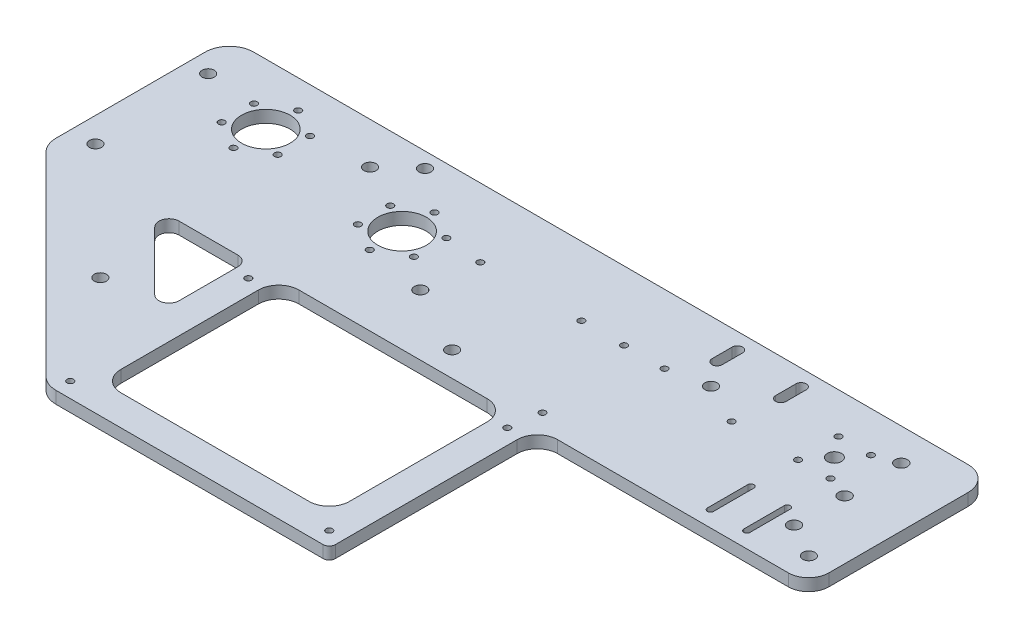
SolidWorks part; units mm, degrees
material "Policarbonato"
ref_plane "Plano frontal" through (0, 0, 0) normal (0, 0, 1) x (1, 0, 0)
ref_plane "Plano superior" through (0, 0, 0) normal (0, 1, 0) x (1, 0, 0)
ref_plane "Plano direito" through (0, 0, 0) normal (1, 0, 0) x (0, 0, -1)
sketch "Esboço1" plane through (0, 0, 0) normal (0, 1, 0) x (1, 0, 0)
  line L3 (-80.5574, -153.6487) -> (51.4721, -153.6487)
  line L4 (54.4721, -150.6487) -> (54.4721, -60.7886)
  line L6 (188.5279, -40.7886) -> (188.5279, 28)
  line L7 (176.5279, 40) -> (-176.5279, 40)
  line L8 (-188.5279, 28) -> (-188.5279, -45.6781)
  line L12 (-122.5768, -50.7886) -> (-93.5279, -50.7886)
  line L13 (-88.5279, -55.7886) -> (-88.5279, -84.8375)
  line L14 (-97.0635, -88.373) -> (-126.1124, -59.3241)
  line L15 (39.4721, -60.6487) -> (39.4721, -128.6487)
  line L16 (29.4721, -138.6487) -> (-63.5279, -138.6487)
  line L17 (-73.5279, -128.6487) -> (-73.5279, -60.6487)
  line L18 (-63.5279, -50.6487) -> (29.4721, -50.6487)
  line L20 (132.5279, 0) -> (148.5279, 0) construction
  line L21 (132.5279, 0) -> (132.5279, 20) construction
  line L22 (132.5279, 20) -> (148.5279, 20) construction
  line L23 (148.5279, 0) -> (148.5279, 20) construction
  line L24 (132.5279, 0) -> (148.5279, 20) construction
  line L25 (132.5279, 20) -> (148.5279, 0) construction
  line L30 (64.4721, -50.7886) -> (178.5279, -50.7886)
  line L31 (150.2221, -43) -> (150.2221, -23) construction
  line L32 (148.7221, -43) -> (148.7221, -23)
  line L33 (151.7221, -43) -> (151.7221, -23)
  line L34 (141.2221, -45.2211) -> (141.2221, -21.4375) construction
  line L36 (132.2221, -43) -> (132.2221, -23) construction
  line L37 (133.7221, -43) -> (133.7221, -23)
  line L38 (130.7221, -43) -> (130.7221, -23)
  line L39 (49.2221, -43) -> (150.2221, -43) construction
  line L40 (54.4721, -120.5) -> (144.9721, -120.5) construction
  line L41 (54.4721, -120.5) -> (54.4721, -7) construction
  line L42 (54.4721, -7) -> (144.9721, -7) construction
  line L43 (144.9721, -120.5) -> (144.9721, -7) construction
  line L44 (54.4721, -120.5) -> (144.9721, -7) construction
  line L45 (54.4721, -7) -> (144.9721, -120.5) construction
  line L46 (70.5279, 22) -> (70.5279, 32) construction
  line L47 (67.9779, 22) -> (67.9779, 32)
  line L48 (73.0779, 22) -> (73.0779, 32)
  line L49 (102.0279, 22) -> (102.0279, 32) construction
  line L50 (99.4779, 22) -> (99.4779, 32)
  line L51 (104.5779, 22) -> (104.5779, 32)
  line L52 (-185.0132, -54.1634) -> (-89.0426, -150.134)
  circle A0 centre (-81.0279, -58.1487) radius 1.6
  circle A1 centre (-81.0279, -146.1487) radius 1.6
  circle A2 centre (46.9721, -58.1487) radius 1.6
  circle A3 centre (46.9721, -146.1487) radius 1.6
  circle A8 centre (176.311, -38.4318) radius 3
  circle A9 centre (0, -38.4318) radius 3
  circle A11 centre (-140.5279, 10) radius 12
  circle A20 centre (-140.5279, 10) radius 16 construction
  circle A21 centre (-140.5279, -6) radius 1.6
  circle A22 centre (-154.3843, 2) radius 1.6
  circle A23 centre (-154.3843, 18) radius 1.6
  circle A24 centre (-84.3674, 32.5) radius 3
  circle A25 centre (-176.311, -38.4318) radius 3
  circle A26 centre (140.5279, 10) radius 3.5
  circle A27 centre (148.5279, 0) radius 1.6
  circle A28 centre (148.5279, 20) radius 1.6
  circle A29 centre (132.5279, 0) radius 1.6
  circle A30 centre (132.5279, 20) radius 1.6
  arc A31 (51.4721, -153.6487) -> (54.4721, -150.6487) centre (51.4721, -150.6487) ccw
  arc A34 (188.5279, 28) -> (176.5279, 40) centre (176.5279, 28) ccw
  arc A35 (-176.5279, 40) -> (-188.5279, 28) centre (-176.5279, 28) ccw
  arc A39 (-93.5279, -50.7886) -> (-88.5279, -55.7886) centre (-93.5279, -55.7886) cw
  arc A40 (-88.5279, -84.8375) -> (-97.0635, -88.373) centre (-93.5279, -84.8375) cw
  arc A41 (-126.1124, -59.3241) -> (-122.5768, -50.7886) centre (-122.5768, -55.7886) cw
  arc A42 (39.4721, -128.6487) -> (29.4721, -138.6487) centre (29.4721, -128.6487) cw
  arc A43 (-63.5279, -138.6487) -> (-73.5279, -128.6487) centre (-63.5279, -128.6487) cw
  arc A44 (-73.5279, -60.6487) -> (-63.5279, -50.6487) centre (-63.5279, -60.6487) cw
  arc A45 (29.4721, -50.6487) -> (39.4721, -60.6487) centre (29.4721, -60.6487) cw
  circle A46 centre (-140.5279, 26) radius 1.6
  circle A47 centre (-126.6715, 18) radius 1.6
  circle A48 centre (-126.6715, 2) radius 1.6
  circle A49 centre (-63.1716, 0) radius 16 construction
  circle A50 centre (-63.1716, -16) radius 1.6
  circle A51 centre (-77.028, -8) radius 1.6
  circle A52 centre (-77.028, 8) radius 1.6
  circle A53 centre (-63.1716, 16) radius 1.6
  circle A54 centre (-49.3152, 8) radius 1.6
  circle A55 centre (-49.3152, -8) radius 1.6
  circle A56 centre (-63.1716, 0) radius 12
  circle A57 centre (-33.5279, -20.6487) radius 3
  circle A58 centre (79.5279, 10) radius 3
  arc A62 (188.5279, -40.7886) -> (178.5279, -50.7886) centre (178.5279, -40.7886) cw
  arc A63 (54.4721, -60.7886) -> (64.4721, -50.7886) centre (64.4721, -60.7886) cw
  arc A64 (148.7221, -43) -> (151.7221, -43) centre (150.2221, -43) ccw
  arc A65 (151.7221, -23) -> (148.7221, -23) centre (150.2221, -23) ccw
  arc A66 (133.7221, -43) -> (130.7221, -43) centre (132.2221, -43) cw
  arc A67 (130.7221, -23) -> (133.7221, -23) centre (132.2221, -23) cw
  circle A68 centre (99.7221, 0) radius 1.6
  circle A69 centre (49.2221, -43) radius 1.6
  circle A70 centre (150.2221, -43) radius 1.6 construction
  circle A71 centre (-30.5279, 6) radius 1.6
  circle A72 centre (19.4721, 6) radius 1.6
  circle A73 centre (60.5279, 6) radius 1.6
  circle A75 centre (40.5279, 6) radius 1.6
  circle A76 centre (70.5279, 27) radius 2.55 construction
  circle A77 centre (102.0279, 27) radius 2.55 construction
  circle A78 centre (159.4679, 24.07) radius 3.05
  circle A79 centre (159.4679, -3.93) radius 3.05
  circle A80 centre (159.4679, -28.93) radius 3.05
  arc A81 (67.9779, 22) -> (73.0779, 22) centre (70.5279, 22) ccw
  arc A82 (73.0779, 32) -> (67.9779, 32) centre (70.5279, 32) ccw
  arc A83 (99.4779, 22) -> (104.5779, 22) centre (102.0279, 22) ccw
  arc A84 (104.5779, 32) -> (99.4779, 32) centre (102.0279, 32) ccw
  circle A85 centre (-178.5279, 19.5) radius 3
  circle A86 centre (-98.5279, 19.5) radius 3
  arc A87 (-80.5574, -153.6487) -> (-89.0426, -150.134) centre (-80.5574, -141.6487) cw
  arc A88 (-185.0132, -54.1634) -> (-188.5279, -45.6781) centre (-176.5279, -45.6781) cw
  point P14 (150.2221, -33)
  point P16 (-188.5279, -49.43)
  point P43 (-140.5279, 10)
  point P70 (-144.4721, -50.6487)
  point P82 (-85.5279, -153.6487)
  point P86 (-108.9113, -77.1615)
  point P87 (-114.6575, -90.236)
  point P88 (-95.7013, -94.8785)
  point P89 (0, 0)
  point P116 (-63.1716, 0)
  point P123 (0, 40)
  point P124 (132.2221, -33)
  point P129 (99.7221, -63.75)
  point P135 (99.7221, -7)
  point P141 (99.7221, -43)
  point P161 (70.5279, 27)
  point P168 (102.0279, 27)
  point P177 (-93.7116, -84.3741)
  dimension "D2" = 3
  dimension "D8" = 12
  dimension "D10" = 12
  dimension "D11" = 61
  dimension "D12" = 203.9448
  dimension "D13" = 7.5
  dimension "D14" = 104.1605
  dimension "D16" = 135.7229
  dimension "D22" = 48.4318
  dimension "D23" = 32
  dimension "D24" = 3.2
  dimension "D25" = 6
  dimension "D26" = 24
  dimension "D27" = 48
  dimension "D28" = 30
  dimension "D29" = 40
  dimension "D30" = 6
  dimension "D34" = 30
  dimension "D31" = 32
  dimension "D32" = 3.2
  dimension "D33" = 24
  dimension "D35" = 6
  dimension "D36" = 155
  dimension "D37" = 30
  dimension "D44" = 7
  dimension "D48" = 10
  dimension "D6" = 10
  dimension "D58" = 5
  dimension "D62" = 1.5
  dimension "D68" = 101
  dimension "D72" = 80
  dimension "D75" = 5.1
  dimension "D80" = 14.07
  dimension "D82" = 6.1
  dimension "D83" = 10
  dimension "D1" = 137
  dimension "D9" = 377.0558
  dimension "D15" = 225
  dimension "D17" = 38
  dimension "D18" = 15
  dimension "D38" = 48
  dimension "D39" = 15
  dimension "D40" = 12.2169
  dimension "D41" = 12.2169
  dimension "D42" = 16
  dimension "D43" = 20
  dimension "D45" = 15
  dimension "D46" = 15
  dimension "D49" = 7.5
  dimension "D50" = 7.5
  dimension "D51" = 88
  dimension "D52" = 128
  dimension "D53" = 93
  dimension "D56" = 20.6487
  dimension "D57" = 68
  dimension "D59" = 10
  dimension "D60" = 20.5
  dimension "D61" = 20
  dimension "D63" = 9
  dimension "D64" = 113.5
  dimension "D65" = 90.5
  dimension "D66" = 7
  dimension "D67" = 43
  dimension "D69" = 34
  dimension "D70" = 110
  dimension "D71" = 50
  dimension "D73" = 20
  dimension "D74" = 31.5
  dimension "D76" = 13
  dimension "D77" = 10
  dimension "D78" = 25
  dimension "D79" = 28
  dimension "D81" = 18.94
  dimension "D84" = 80
extrude "Ressalto-extrusão1" add sketch "Esboço1" against normal blind 6
sketch "Esboço2" plane through (0, 0, 0) normal (0, 1, 0) x (1, 0, 0)
  line L1 (-126.1124, -59.3241) -> (-97.0635, -88.373) construction
  line L2 (-131.2731, -107.9035) -> (-104.403, -81.0335) construction
  line L3 (-185.0132, -54.1634) -> (-89.0426, -150.134) construction
  circle A1 centre (-117.8381, -94.4685) radius 3
  arc A2 (-188.5279, -45.6781) -> (-185.0132, -54.1634) centre (-176.5279, -45.6781) ccw construction
  point P0 (-108.1215, -90.5113)
  point P1 (-117.8381, -94.4685)
  dimension "D1" = 76
  dimension "D2" = 6
extrude "Corte-extrusão1" cut sketch "Esboço2" against normal blind 10
